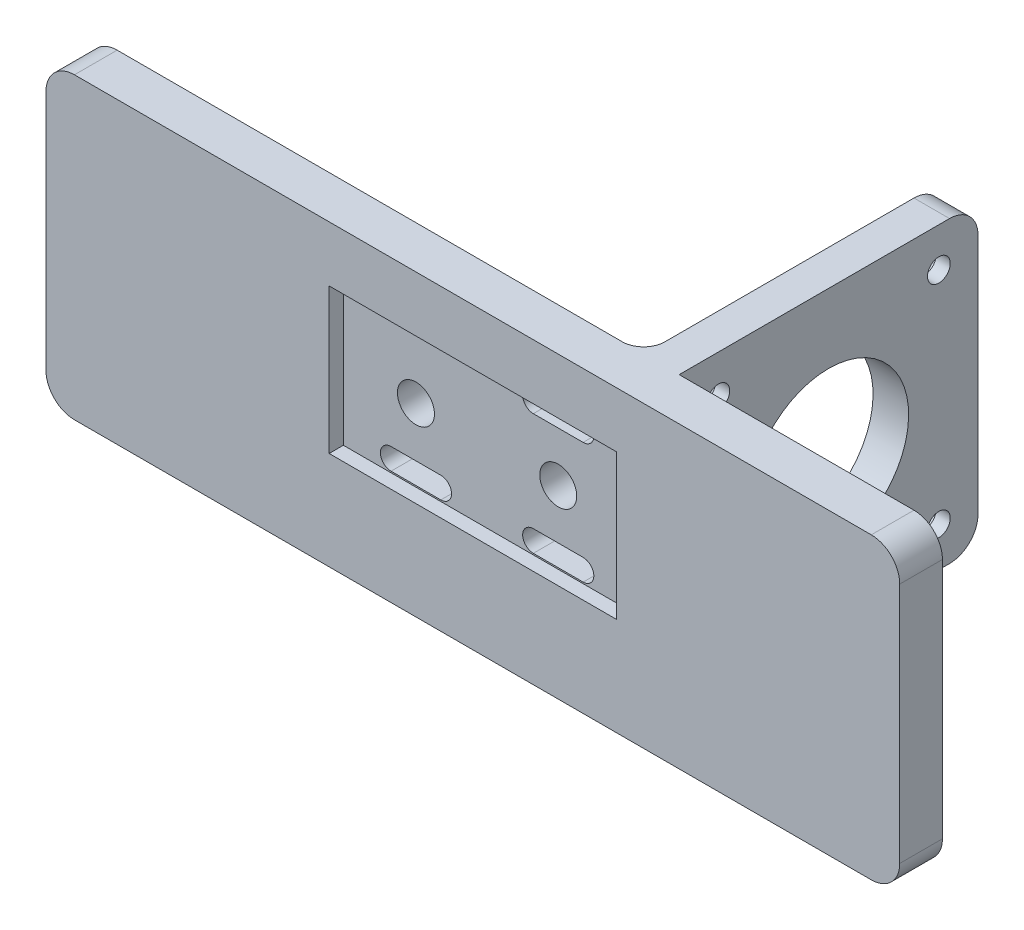
SolidWorks part; units mm, degrees
ref_plane "Front Plane" through (0, 0, 0) normal (0, 0, 1) x (1, 0, 0)
ref_plane "Top Plane" through (0, 0, 0) normal (0, 1, 0) x (1, 0, 0)
ref_plane "Right Plane" through (0, 0, 0) normal (1, 0, 0) x (0, 0, -1)
sketch "Sketch1" plane through (0, 0, 0) normal (0, 0, 1) x (1, 0, 0)
  line L0 (-10, 22.5) -> (10, 22.5) construction
  line L7 (-56, -1.5) -> (20, -1.5)
  line L8 (-60, 2.5) -> (-60, 36.5)
  line L9 (-56, 40.5) -> (56, 40.5)
  line L10 (60, 36.5) -> (60, 2.5)
  line L11 (20, -1.5) -> (56, -1.5)
  line L12 (-10, 22.5) -> (-10, 14) construction
  line L13 (-20, 12.5) -> (20, 12.5) construction
  line L14 (-20, 12.5) -> (-20, 32.5) construction
  line L15 (-20, 32.5) -> (20, 32.5) construction
  line L16 (20, 12.5) -> (20, 32.5) construction
  line L17 (-13.5, 14) -> (-6.5, 14) construction
  line L18 (0, 29) -> (0, 16) construction
  line L19 (-13.5, 15.5) -> (-6.5, 15.5)
  line L20 (-13.5, 12.5) -> (-6.5, 12.5)
  line L21 (13.5, 14) -> (6.5, 14) construction
  line L24 (13.5, 15.5) -> (6.5, 15.5)
  line L25 (13.5, 12.5) -> (6.5, 12.5)
  line L26 (13.5, 31) -> (6.5, 31) construction
  line L27 (13.5, 29.5) -> (6.5, 29.5)
  line L28 (13.5, 32.5) -> (6.5, 32.5)
  circle A0 centre (10, 22.5) radius 2.6
  circle A1 centre (-10, 22.5) radius 2.6
  arc A2 (56, -1.5) -> (60, 2.5) centre (56, 2.5) ccw
  arc A3 (56, 40.5) -> (60, 36.5) centre (56, 36.5) cw
  arc A4 (-56, -1.5) -> (-60, 2.5) centre (-56, 2.5) cw
  arc A5 (-60, 36.5) -> (-56, 40.5) centre (-56, 36.5) cw
  arc A6 (-13.5, 15.5) -> (-13.5, 12.5) centre (-13.5, 14) ccw
  arc A7 (-6.5, 12.5) -> (-6.5, 15.5) centre (-6.5, 14) ccw
  arc A10 (13.5, 15.5) -> (13.5, 12.5) centre (13.5, 14) cw
  arc A11 (6.5, 12.5) -> (6.5, 15.5) centre (6.5, 14) cw
  arc A12 (13.5, 29.5) -> (13.5, 32.5) centre (13.5, 31) ccw
  arc A13 (6.5, 32.5) -> (6.5, 29.5) centre (6.5, 31) ccw
  point P0 (0, 16)
  point P2 (0, 22.5)
  point P10 (0, 22.5)
  point P15 (0, 0)
  point P23 (-60, -1.5)
  point P26 (-60, 40.5)
  point P32 (-10, 14)
  point P38 (0, 22.5)
  point P40 (10, 14)
  point P45 (-20, 22.5)
  point P48 (10, 31)
  dimension "D3" = 5.2
  dimension "D4" = 40
  dimension "D6" = 4
  dimension "D1" = 18
  dimension "D2" = 20
  dimension "D5" = 42
  dimension "D7" = 8.5
extrude "Boss-Extrude1" add sketch "Sketch1" along normal blind 6
sketch "Sketch8" plane through (0, 0, 6) normal (0, 0, 1) x (1, 0, 0)
  line L46 (20.2, 12.3) -> (20.2, 32.7)
  line L47 (-20.2, 12.3) -> (20.2, 12.3)
  line L48 (-20.2, 32.7) -> (-20.2, 12.3)
  line L49 (20.2, 32.7) -> (-20.2, 32.7)
  line L50 (20.2, 12.3) -> (20.2, 32.7)
  line L51 (-20.2, 12.3) -> (20.2, 12.3)
  line L52 (-20.2, 32.7) -> (-20.2, 12.3)
  line L53 (20.2, 32.7) -> (-20.2, 32.7)
  dimension "D1" = 0.2
extrude "Cut-Extrude4" cut sketch "Sketch8" against normal blind 2
sketch "Sketch9" plane through (0, 0, 0) normal (0, 0, -1) x (-1, 0, 0)
  line L0 (-10, 22.5) -> (-18, 22.5) construction
  line L2 (-18, 40.5) -> (-23, 40.5)
  line L3 (-18, 40.5) -> (-18, -1.5)
  line L4 (-18, -1.5) -> (-23, -1.5)
  line L5 (-23, 40.5) -> (-23, -1.5)
  dimension "D1" = 8
  dimension "D2" = 5
  dimension "D3" = 18
extrude "Boss-Extrude2" add sketch "Sketch9" along normal blind 42
fillet "Fillet1" radius 4 2 edges at (20.5, -1.5, -42) (20.5, 40.5, -42)
fillet "Fillet2" radius 3 1 edges at (18, 19.5, 0)
sketch "Sketch10" plane through (23, 0, 0) normal (1, 0, 0) x (0, 0, -1)
  line L0 (42, 19.5) -> (0, 19.5) construction
  line L1 (42, 36.5) -> (42, 2.5) construction
  line L2 (0, 2.5) -> (0, 36.5) construction
  line L4 (5.5, 4) -> (36.5, 4) construction
  line L5 (5.5, 4) -> (5.5, 35) construction
  line L6 (5.5, 35) -> (36.5, 35) construction
  line L7 (36.5, 4) -> (36.5, 35) construction
  line L8 (5.5, 4) -> (36.5, 35) construction
  line L9 (5.5, 35) -> (36.5, 4) construction
  circle A0 centre (21, 19.5) radius 11.25
  circle A1 centre (5.5, 35) radius 1.6
  circle A2 centre (36.5, 35) radius 1.6
  circle A3 centre (36.5, 4) radius 1.6
  circle A4 centre (5.5, 4) radius 1.6
  dimension "D1" = 22.5
  dimension "D3" = 3.2
  dimension "D2" = 31
extrude "Cut-Extrude5" cut sketch "Sketch10" against normal blind 42
sketch "Sketch11" plane through (18, 0, 0) normal (-1, 0, 0) x (0, 0, 1)
  circle A0 centre (-36.5, 35) radius 2.8
  circle A1 centre (-5.5, 35) radius 2.8
  circle A2 centre (-5.5, 4) radius 2.8
  circle A3 centre (-36.5, 4) radius 2.8
  dimension "D1" = 5.6
extrude "Cut-Extrude6" cut sketch "Sketch11" against normal blind 3 and the other way blind 3
